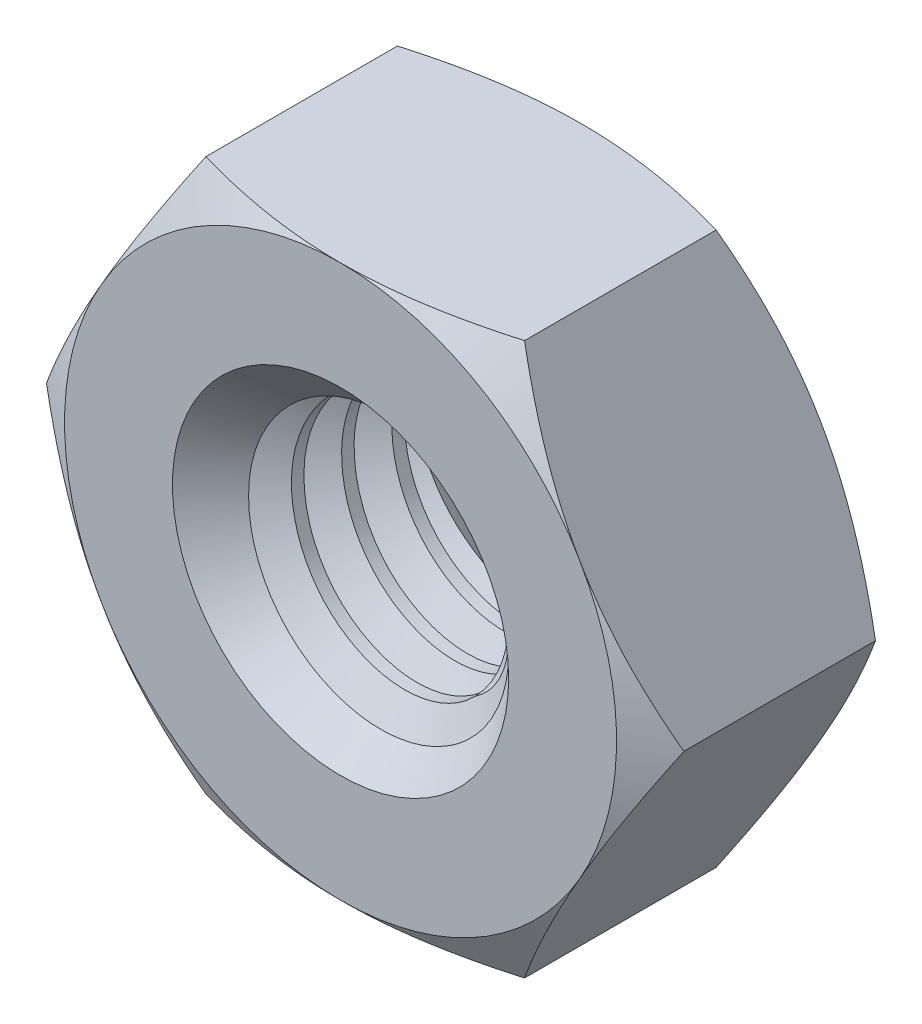
SolidWorks part; units mm, degrees
ref_plane "Front" through (0, 0, 0) normal (0, 0, 1) x (1, 0, 0)
ref_plane "Top" through (0, 0, 0) normal (0, 1, 0) x (1, 0, 0)
ref_plane "Right" through (0, 0, 0) normal (1, 0, 0) x (0, 0, -1)
sketch "Çizim1" plane through (0, 0, 0) normal (0, 0, 1) x (1, 0, 0)
  line L1 (3.1754, 0) -> (1.5877, 2.75)
  line L2 (1.5877, 2.75) -> (-1.5877, 2.75)
  line L3 (-1.5877, 2.75) -> (-3.1754, 0)
  line L4 (-3.1754, 0) -> (-1.5877, -2.75)
  line L5 (-1.5877, -2.75) -> (1.5877, -2.75)
  line L6 (1.5877, -2.75) -> (3.1754, 0)
  circle A0 centre (0, 0) radius 2.75 construction
  dimension "D1" = 5.5
extrude "Yükseklik-Ekstrüzyon1" add sketch "Çizim1" along normal blind 2.4
sketch "Çizim2" plane through (0, 0, 2.4) normal (0, 0, 1) x (1, 0, 0)
  circle A0 centre (0, 0) radius 2.75
extrude "Kes-Ekstrüzyon1" cut sketch "Çizim2" against normal blind 2.4 draft 60 flip side to cut
sketch "Çizim3" plane through (0, 0, 0) normal (0, 0, -1) x (-1, 0, 0)
  circle A0 centre (0, 0) radius 2.75
extrude "Kes-Ekstrüzyon2" cut sketch "Çizim3" against normal blind 2.4 draft 60 flip side to cut
sketch "Çizim4" plane through (0, 0, 0) normal (0, 0, -1) x (-1, 0, 0)
  circle A0 centre (0, 0) radius 1.175
  dimension "D1" = 2.35
extrude "Kes-Ekstrüzyon3" cut sketch "Çizim4" against normal blind 2.4
chamfer "Pah1" distance 0.5 angle 45 2 edges at (-1.175, 0, 2.4) (-1.175, 0, 0)
sketch "Çizim5" plane through (0, 0, 2.4) normal (0, 0, 1) x (1, 0, 0)
  circle A0 centre (0, 0) radius 1.175
curve "Helis/Spiral1" pitch 0.5 height 3 radius 1.175 centre (0, 0, 2.4) axis (0, 0, -1) start towards (-1, 0, 0)
ref_plane "Düzlem1" through (-1.175, 0, -0.6) normal (0, 0.9977, -0.0676) x (1, 0, 0)
sketch "Çizim6" plane through (-1.175, 0, -0.6) normal (0, 0.9977, -0.0676) x (1, 0, 0)
  line L1 (-0.325, 0) -> (0.0987, -0.2446)
  line L3 (0.0987, 0.2446) -> (-0.325, 0)
  line L4 (0.0987, 0.2446) -> (0.0987, -0.2446)
  line L5 (0.1625, 0) -> (0.1625, 0.2815) [skipped]
  circle A0 centre (0, 0) radius 0.1625 construction
  dimension "D1" = 0.325
sweep "Kes-Süpür1" cut profiles "Çizim6" path "Helis/Spiral1" align with end faces yes
